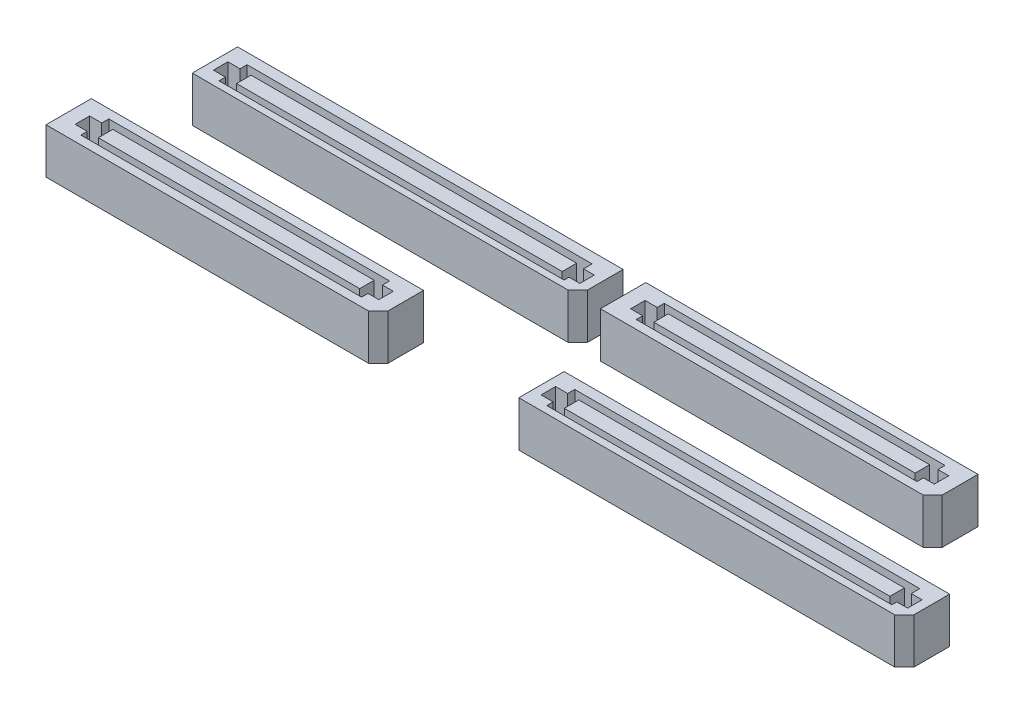
SolidWorks part; units mm, degrees
ref_plane "Front Plane" through (0, 0, 0) normal (0, 0, 1) x (1, 0, 0)
ref_plane "Top Plane" through (0, 0, 0) normal (0, 1, 0) x (1, 0, 0)
ref_plane "Right Plane" through (0, 0, 0) normal (1, 0, 0) x (0, 0, -1)
ref_plane "Plane1" through (0, -1.6866, 0) normal (0, 1, 0) x (1, 0, 0)
ref_plane "center-of-slot" through (0, -0.8433, 0) normal (0, 1, 0) x (1, 0, 0)
sketch "Sketch1" plane through (0, 0, 0) normal (0, 1, 0) x (1, 0, 0)
  line L0 (55.811, 9.5) -> (97.25, 9.5)
  line L1 (3.686, 9.5) -> (39.25, 9.5)
  line L2 (2.625, 8.439) -> (2.625, 4.5)
  line L3 (2.625, 4.5) -> (39.25, 4.5) construction
  line L4 (39.25, 9.5) -> (39.25, 4.5) construction
  line L5 (0, 0) -> (100, 0) construction
  line L6 (0, 0) -> (0, 75) construction
  line L7 (0, 75) -> (100, 75) construction
  line L8 (100, 0) -> (100, 75) construction
  line L9 (54.75, 8.439) -> (54.75, 4.5)
  line L10 (54.75, 4.5) -> (97.25, 4.5) construction
  line L11 (97.25, 9.5) -> (97.25, 4.5) construction
  line L12 (51.811, 22.5) -> (87.375, 22.5)
  line L13 (6.811, 22.5) -> (48.25, 22.5)
  line L14 (5.75, 21.439) -> (5.75, 17.5)
  line L15 (5.75, 17.5) -> (48.25, 17.5) construction
  line L16 (48.25, 22.5) -> (48.25, 17.5) construction
  line L17 (50.75, 21.439) -> (50.75, 17.5)
  line L18 (50.75, 17.5) -> (87.375, 17.5) construction
  line L19 (87.375, 22.5) -> (87.375, 17.5) construction
  line L20 (5.75, 21.439) -> (6.811, 22.5) construction
  line L21 (50.75, 21.439) -> (51.811, 22.5) construction
  line L22 (54.75, 8.439) -> (55.811, 9.5) construction
  line L23 (2.625, 8.439) -> (3.686, 9.5) construction
  line L24 (2.625, 4.5) -> (38.195, 4.5)
  line L25 (38.195, 4.5) -> (39.25, 5.555)
  line L26 (39.25, 5.555) -> (39.25, 9.5)
  line L27 (50.75, 17.5) -> (86.32, 17.5)
  line L28 (86.32, 17.5) -> (87.375, 18.555)
  line L29 (87.375, 18.555) -> (87.375, 22.5)
  line L30 (54.75, 4.5) -> (96.19, 4.5)
  line L31 (96.19, 4.5) -> (97.25, 5.56)
  line L32 (97.25, 5.56) -> (97.25, 9.5)
  line L33 (5.75, 17.5) -> (47.19, 17.5)
  line L34 (47.19, 17.5) -> (48.25, 18.56)
  line L35 (48.25, 18.56) -> (48.25, 22.5)
  line L36 (5.75, 21.439) -> (5.75, 22.5)
  line L37 (5.75, 22.5) -> (6.811, 22.5)
  line L38 (2.625, 8.439) -> (2.625, 9.5)
  line L39 (2.625, 9.5) -> (3.686, 9.5)
  line L40 (54.75, 8.439) -> (54.75, 9.5)
  line L41 (54.75, 9.5) -> (55.811, 9.5)
  line L42 (50.75, 21.439) -> (50.75, 22.5)
  line L43 (50.75, 22.5) -> (51.811, 22.5)
  point P0 (2.625, 9.5)
  point P9 (54.75, 9.5)
  point P13 (5.75, 22.5)
  point P17 (50.75, 22.5)
extrude "SV" add sketch "Sketch1" along normal blind 5
sketch "Sketch3" plane through (0, 5, 0) normal (0, 1, 0) x (1, 0, 0)
  line L0 (4.1893, 7.7457) -> (5.5243, 7.7457)
  line L1 (4.1893, 8.5242) -> (37.667, 8.5242) construction
  line L2 (4.1893, 8.5242) -> (4.1893, 5.4386) construction
  line L3 (4.1893, 5.4386) -> (37.667, 5.4386) construction
  line L4 (37.667, 8.5242) -> (37.667, 5.4386) construction
  line L5 (5.5243, 7.7457) -> (5.5243, 8.5242)
  line L6 (5.5243, 8.5242) -> (36.4757, 8.5242)
  line L7 (36.4757, 8.5242) -> (36.4757, 7.7457)
  line L8 (36.4757, 7.7457) -> (37.667, 7.7457)
  line L9 (37.667, 7.7457) -> (37.667, 6.1479)
  line L10 (37.667, 6.1479) -> (36.4757, 6.1479)
  line L11 (36.4757, 6.1479) -> (36.4757, 5.4386)
  line L12 (36.4757, 5.4386) -> (5.5243, 5.4386)
  line L13 (5.5243, 5.4386) -> (5.5243, 6.1479)
  line L14 (5.5243, 6.1479) -> (4.1893, 6.1479)
  line L15 (4.1893, 6.1479) -> (4.1893, 7.7457)
  line L16 (52.4211, 20.7536) -> (53.7561, 20.7536)
  line L17 (6.7471, 7.7457) -> (35.5588, 7.7457)
  line L18 (6.7471, 7.7457) -> (6.7471, 6.1479)
  line L19 (6.7471, 6.1479) -> (35.5588, 6.1479)
  line L20 (35.5588, 7.7457) -> (35.5588, 6.1479)
  line L21 (52.4211, 21.532) -> (85.8988, 21.532) construction
  line L22 (52.4211, 21.532) -> (52.4211, 18.4464) construction
  line L23 (52.4211, 18.4464) -> (85.8988, 18.4464) construction
  line L24 (85.8988, 21.532) -> (85.8988, 18.4464) construction
  line L25 (53.7561, 20.7536) -> (53.7561, 21.532)
  line L26 (53.7561, 21.532) -> (84.7075, 21.532)
  line L27 (84.7075, 21.532) -> (84.7075, 20.7536)
  line L28 (84.7075, 20.7536) -> (85.8988, 20.7536)
  line L29 (85.8988, 20.7536) -> (85.8988, 19.1558)
  line L30 (85.8988, 19.1558) -> (84.7075, 19.1558)
  line L31 (84.7075, 19.1558) -> (84.7075, 18.4464)
  line L32 (84.7075, 18.4464) -> (53.7561, 18.4464)
  line L33 (53.7561, 18.4464) -> (53.7561, 19.1558)
  line L34 (53.7561, 19.1558) -> (52.4211, 19.1558)
  line L35 (52.4211, 19.1558) -> (52.4211, 20.7536)
  line L36 (54.9789, 20.7536) -> (83.7906, 20.7536)
  line L37 (54.9789, 20.7536) -> (54.9789, 19.1558)
  line L38 (54.9789, 19.1558) -> (83.7906, 19.1558)
  line L39 (83.7906, 20.7536) -> (83.7906, 19.1558)
  line L40 (55.7059, 7.599) -> (57.0409, 7.599)
  line L41 (55.7059, 8.3775) -> (96.2696, 8.3775) construction
  line L42 (55.7059, 8.3775) -> (55.7059, 5.2919) construction
  line L43 (55.7059, 5.2919) -> (96.2696, 5.2919) construction
  line L44 (96.2696, 8.3775) -> (96.2696, 5.2919) construction
  line L45 (57.0409, 7.599) -> (57.0409, 8.3775)
  line L46 (57.0409, 8.3775) -> (95.0783, 8.3775)
  line L47 (95.0783, 8.3775) -> (95.0783, 7.4377)
  line L48 (95.0783, 7.4377) -> (96.2696, 7.4377)
  line L49 (96.2696, 7.4377) -> (96.2696, 5.8399)
  line L50 (96.2696, 5.8399) -> (95.0783, 5.8399)
  line L51 (95.0783, 5.8399) -> (95.0783, 5.2919)
  line L52 (95.0783, 5.2919) -> (57.0409, 5.2919)
  line L53 (57.0409, 5.2919) -> (57.0409, 6.0012)
  line L54 (57.0409, 6.0012) -> (55.7059, 6.0012)
  line L55 (55.7059, 6.0012) -> (55.7059, 7.599)
  line L56 (58.2637, 7.599) -> (94.1615, 7.599)
  line L57 (58.2637, 7.599) -> (58.2637, 6.0012)
  line L58 (58.2637, 6.0012) -> (94.1615, 6.0012)
  line L59 (94.1615, 7.599) -> (94.1615, 6.0012)
  line L60 (6.6366, 20.5397) -> (7.9716, 20.5397)
  line L61 (6.6366, 21.3182) -> (47.2003, 21.3182) construction
  line L62 (6.6366, 21.3182) -> (6.6366, 18.2325) construction
  line L63 (6.6366, 18.2325) -> (47.2003, 18.2325) construction
  line L64 (47.2003, 21.3182) -> (47.2003, 18.2325) construction
  line L65 (7.9716, 20.5397) -> (7.9716, 21.3182)
  line L66 (7.9716, 21.3182) -> (46.009, 21.3182)
  line L67 (46.009, 21.3182) -> (46.009, 20.3784)
  line L68 (46.009, 20.3784) -> (47.2003, 20.3784)
  line L69 (47.2003, 20.3784) -> (47.2003, 18.7806)
  line L70 (47.2003, 18.7806) -> (46.009, 18.7806)
  line L71 (46.009, 18.7806) -> (46.009, 18.2325)
  line L72 (46.009, 18.2325) -> (7.9716, 18.2325)
  line L73 (7.9716, 18.2325) -> (7.9716, 18.9419)
  line L74 (7.9716, 18.9419) -> (6.6366, 18.9419)
  line L75 (6.6366, 18.9419) -> (6.6366, 20.5397)
  line L76 (9.1944, 20.5397) -> (45.0922, 20.5397)
  line L77 (9.1944, 20.5397) -> (9.1944, 18.9419)
  line L78 (9.1944, 18.9419) -> (45.0922, 18.9419)
  line L79 (45.0922, 20.5397) -> (45.0922, 18.9419)
extrude "Cut-Extrude1" cut sketch "Sketch3" against normal blind 4
sketch "Sketch6" [suppressed] plane through (0, -1.6866, 0) normal (0, 1, 0) x (1, 0, 0)
  line L0 (2.625, 4.5) -> (2.625, 9.5) construction
  line L1 (5.75, 22.5) -> (48.25, 22.5) construction
  line L2 (5.75, 22.5) -> (5.75, 17.5) construction
  line L3 (5.75, 17.5) -> (48.25, 17.5) construction
  line L4 (48.25, 22.5) -> (48.25, 17.5) construction
  line L5 (50.75, 22.5) -> (87.375, 22.5) construction
  line L6 (50.75, 22.5) -> (50.75, 17.5) construction
  line L7 (50.75, 17.5) -> (87.375, 17.5) construction
  line L8 (87.375, 22.5) -> (87.375, 17.5) construction
  line L9 (97.25, 9.5) -> (54.75, 9.5) construction
  line L10 (97.25, 9.5) -> (97.25, 4.5) construction
  line L11 (97.25, 4.5) -> (54.75, 4.5) construction
  line L12 (54.75, 9.5) -> (54.75, 4.5) construction
  line L13 (39.25, 9.5) -> (2.625, 9.5) construction
  line L14 (39.25, 9.5) -> (39.25, 4.5) construction
  line L15 (39.25, 4.5) -> (2.625, 4.5) construction
  line L16 (2.625, 9.5) -> (2.625, 4.5) construction
  line L17 (2.625, 4.5) -> (38.195, 4.5)
  line L18 (2.625, 9.5) -> (39.25, 9.5) construction
  line L19 (48.25, 18.5619) -> (47.1881, 17.5) construction
  line L20 (39.25, 5.555) -> (39.25, 9.5)
  line L21 (48.25, 18.5619) -> (48.25, 22.5)
  line L22 (47.1881, 17.5) -> (5.75, 17.5)
  line L23 (39.25, 5.555) -> (38.195, 4.5) construction
  line L24 (54.75, 4.5) -> (96.19, 4.5)
  line L25 (96.19, 4.5) -> (97.25, 5.56) construction
  line L26 (97.25, 5.56) -> (97.25, 9.5)
  line L27 (50.75, 17.5) -> (86.32, 17.5)
  line L28 (86.32, 17.5) -> (87.375, 18.555) construction
  line L29 (87.375, 18.555) -> (87.375, 22.5)
  line L30 (2.625, 4.5) -> (2.625, 8.44)
  line L31 (2.625, 8.44) -> (3.685, 9.5)
  line L32 (3.685, 9.5) -> (39.25, 9.5)
  line L33 (5.75, 17.5) -> (5.75, 21.44)
  line L34 (5.75, 21.44) -> (6.81, 22.5)
  line L35 (6.81, 22.5) -> (48.25, 22.5)
  line L36 (54.75, 4.5) -> (54.75, 8.44)
  line L37 (54.75, 8.44) -> (55.81, 9.5)
  line L38 (55.81, 9.5) -> (97.25, 9.5)
  line L39 (87.375, 22.5) -> (51.805, 22.5)
  line L40 (51.805, 22.5) -> (50.75, 21.445)
  line L41 (50.75, 21.445) -> (50.75, 17.5)
  line L42 (47.1881, 17.5) -> (48.25, 17.5)
  line L43 (48.25, 17.5) -> (48.25, 18.5619)
  line L44 (38.195, 4.5) -> (39.25, 4.5)
  line L45 (39.25, 4.5) -> (39.25, 5.555)
  line L46 (96.19, 4.5) -> (97.25, 4.5)
  line L47 (97.25, 4.5) -> (97.25, 5.56)
  line L48 (86.32, 17.5) -> (87.375, 17.5)
  line L49 (87.375, 17.5) -> (87.375, 18.555)
  point P0 (5.75, 22.5)
  point P6 (50.75, 22.5)
  point P15 (54.75, 9.5)
extrude "SV4(a)" [suppressed] add sketch "Sketch6" against normal blind 4 separate body
sketch "Sketch7" [suppressed] plane through (0, -5.6866, 0) normal (0, -1, 0) x (1, 0, 0)
  line L0 (7.9716, -21.3182) -> (7.9716, -20.5397)
  line L1 (7.9716, -20.5397) -> (6.6366, -20.5397)
  line L2 (6.6366, -20.5397) -> (6.6366, -18.9419)
  line L3 (6.6366, -18.9419) -> (7.9716, -18.9419)
  line L4 (7.9716, -18.9419) -> (7.9716, -18.2325)
  line L6 (7.9716, -18.2325) -> (46.009, -18.2325)
  line L7 (46.009, -18.2325) -> (46.009, -18.7806)
  line L8 (46.009, -18.7806) -> (47.2003, -18.7806)
  line L9 (47.2003, -18.7806) -> (47.2003, -20.3784)
  line L10 (47.2003, -20.3784) -> (46.009, -20.3784)
  line L11 (46.009, -20.3784) -> (46.009, -21.3182)
  line L12 (46.009, -21.3182) -> (7.9716, -21.3182)
  line L13 (53.7561, -21.532) -> (84.7075, -21.532)
  line L14 (9.1944, -20.5397) -> (45.0922, -20.5397)
  line L15 (9.1944, -20.5397) -> (9.1944, -18.9419)
  line L16 (9.1944, -18.9419) -> (45.0922, -18.9419)
  line L17 (45.0922, -20.5397) -> (45.0922, -18.9419)
  line L18 (54.9789, -20.7536) -> (83.7906, -20.7536)
  line L19 (54.9789, -20.7536) -> (54.9789, -19.1558)
  line L20 (54.9789, -19.1558) -> (83.7906, -19.1558)
  line L21 (83.7906, -20.7536) -> (83.7906, -19.1558)
  line L22 (94.1615, -7.599) -> (58.2637, -7.599)
  line L23 (94.1615, -7.599) -> (94.1615, -6.0012)
  line L24 (94.1615, -6.0012) -> (58.2637, -6.0012)
  line L25 (58.2637, -7.599) -> (58.2637, -6.0012)
  line L26 (35.5588, -7.7457) -> (6.7471, -7.7457)
  line L27 (35.5588, -7.7457) -> (35.5588, -6.1479)
  line L28 (35.5588, -6.1479) -> (6.7471, -6.1479)
  line L29 (6.7471, -7.7457) -> (6.7471, -6.1479)
  line L30 (84.7075, -21.532) -> (84.7075, -20.7536)
  line L31 (84.7075, -20.7536) -> (85.8988, -20.7536)
  line L32 (85.8988, -20.7536) -> (85.8988, -19.1558)
  line L33 (85.8988, -19.1558) -> (84.7075, -19.1558)
  line L34 (84.7075, -19.1558) -> (84.7075, -18.4464)
  line L35 (84.7075, -18.4464) -> (53.7561, -18.4464)
  line L36 (53.7561, -18.4464) -> (53.7561, -19.1558)
  line L37 (53.7561, -19.1558) -> (52.4211, -19.1558)
  line L38 (52.4211, -19.1558) -> (52.4211, -20.7536)
  line L39 (52.4211, -20.7536) -> (53.7561, -20.7536)
  line L40 (53.7561, -20.7536) -> (53.7561, -21.532)
  line L41 (57.0409, -8.3775) -> (57.0409, -7.599)
  line L42 (57.0409, -7.599) -> (55.7059, -7.599)
  line L43 (55.7059, -7.599) -> (55.7059, -6.0012)
  line L44 (55.7059, -6.0012) -> (57.0409, -6.0012)
  line L45 (57.0409, -6.0012) -> (57.0409, -5.2919)
  line L46 (57.0409, -5.2919) -> (95.0783, -5.2919)
  line L47 (95.0783, -5.2919) -> (95.0783, -5.8399)
  line L48 (95.0783, -5.8399) -> (96.2696, -5.8399)
  line L49 (96.2696, -5.8399) -> (96.2696, -7.4377)
  line L50 (96.2696, -7.4377) -> (95.0783, -7.4377)
  line L51 (95.0783, -7.4377) -> (95.0783, -8.3775)
  line L52 (95.0783, -8.3775) -> (57.0409, -8.3775)
  line L53 (4.1893, -6.1479) -> (5.5243, -6.1479)
  line L54 (5.5243, -6.1479) -> (5.5243, -5.4386)
  line L55 (5.5243, -5.4386) -> (36.4757, -5.4386)
  line L56 (36.4757, -5.4386) -> (36.4757, -6.1479)
  line L57 (36.4757, -6.1479) -> (37.667, -6.1479)
  line L58 (37.667, -6.1479) -> (37.667, -7.7457)
  line L59 (37.667, -7.7457) -> (36.4757, -7.7457)
  line L60 (36.4757, -7.7457) -> (36.4757, -8.5242)
  line L61 (36.4757, -8.5242) -> (5.5243, -8.5242)
  line L62 (5.5243, -8.5242) -> (5.5243, -7.7457)
  line L63 (5.5243, -7.7457) -> (4.1893, -7.7457)
  line L64 (4.1893, -7.7457) -> (4.1893, -6.1479)
extrude "SV4(b)" [suppressed] add sketch "Sketch7" along normal blind 4
